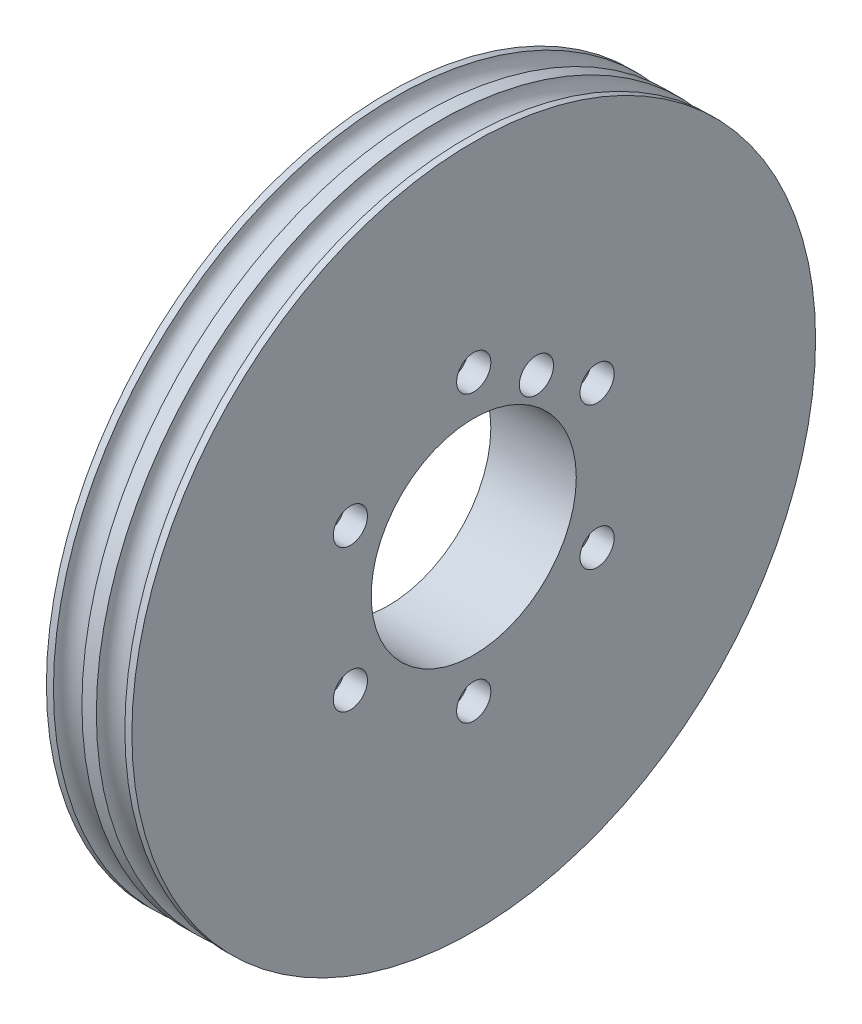
SolidWorks part; units mm, degrees
ref_plane "Front Plane" through (0, 0, 0) normal (0, 0, 1) x (1, 0, 0)
ref_plane "Top Plane" through (0, 0, 0) normal (0, 1, 0) x (1, 0, 0)
ref_plane "Right Plane" through (0, 0, 0) normal (1, 0, 0) x (0, 0, -1)
sketch "Sketch1" plane through (0, 0, 0) normal (1, 0, 0) x (0, 0, -1)
  circle A0 centre (0, 0) radius 18
  circle A1 centre (0, 0) radius 60
  dimension "D1" = 36
  dimension "D2" = 120
extrude "Boss-Extrude1" add sketch "Sketch1" along normal mid plane 15
sketch "Sketch3" plane through (7.5, 0, 0) normal (1, 0, 0) x (0, 0, -1)
  line L0 (0, 0) -> (0, 25) construction
  circle A0 centre (0, 25) radius 2
  circle A1 centre (21.6506, 12.5) radius 2
  circle A2 centre (21.6506, -12.5) radius 2
  circle A3 centre (0, -25) radius 2
  circle A4 centre (-21.6506, -12.5) radius 2
  circle A5 centre (-21.6506, 12.5) radius 2
  point P20 (0, 0)
  dimension "D1" = 25
  dimension "D2" = 6
extrude "Cut-Extrude2" cut sketch "Sketch3" against normal up to next
sketch "Sketch4" plane through (-7.5, 0, 0) normal (-1, 0, 0) x (0, 0, 1)
  circle A0 centre (0, 0) radius 31.5
  circle A1 centre (0, 0) radius 33
  circle A2 centre (0, 0) radius 30
  dimension "D1" = 1.5
  dimension "D2" = 1.5
extrude "Cut-Extrude3" cut sketch "Sketch4" against normal blind 3 contours A1 A0 | A0 A2 region at (-7.5, 0, -30.609) region at (-7.5, 0, -32.0666)
sketch "Sketch5" plane through (0, 0, 0) normal (0, 0, 1) x (1, 0, 0)
  line L0 (0, 58.4096) -> (0, 61.7624) construction
  line L1 (0, -60) -> (0, 60) construction
  line L7 (7.5338, 60.0138) -> (0, 60.0138) construction
  circle A0 centre (3.7669, 60.0138) radius 2.5
  circle A1 centre (-3.7669, 60.0138) radius 2.5
  point P8 (0, 0)
  point P9 (3.7669, 60.0138)
  dimension "D1" = 5
ref_axis "Axis1" through (7.5, 0, 0) along (-1, 0, 0)
revolve "Cut-Revolve2" cut sketch "Sketch5" angle 360 about axis through (7.5, 0, 0) along (-1, 0, 0)
sketch "Sketch6" plane through (7.5, 0, 0) normal (1, 0, 0) x (0, 0, -1)
  circle A8 centre (0, 25) radius 3
  circle A9 centre (21.6506, 12.5) radius 3
  circle A10 centre (21.6506, -12.5) radius 3
  circle A11 centre (0, -25) radius 3
  circle A12 centre (-21.6506, -12.5) radius 3
  circle A13 centre (-21.6506, 12.5) radius 3
  point P16 (0, 0)
extrude "Cut-Extrude4" cut sketch "Sketch6" against normal blind 4
sketch "Sketch7" plane through (-7.5, 0, 0) normal (-1, 0, 0) x (0, 0, 1)
  line L0 (0, 0) -> (-11, 19.0526) construction
  line L1 (0, 0) -> (0, 2.9604) construction
  circle A1 centre (-11, 19.0526) radius 3
  point P11 (0, 0)
  dimension "D1" = 30
  dimension "D3" = 22
extrude "Cut-Extrude5" cut sketch "Sketch7" against normal up to next
